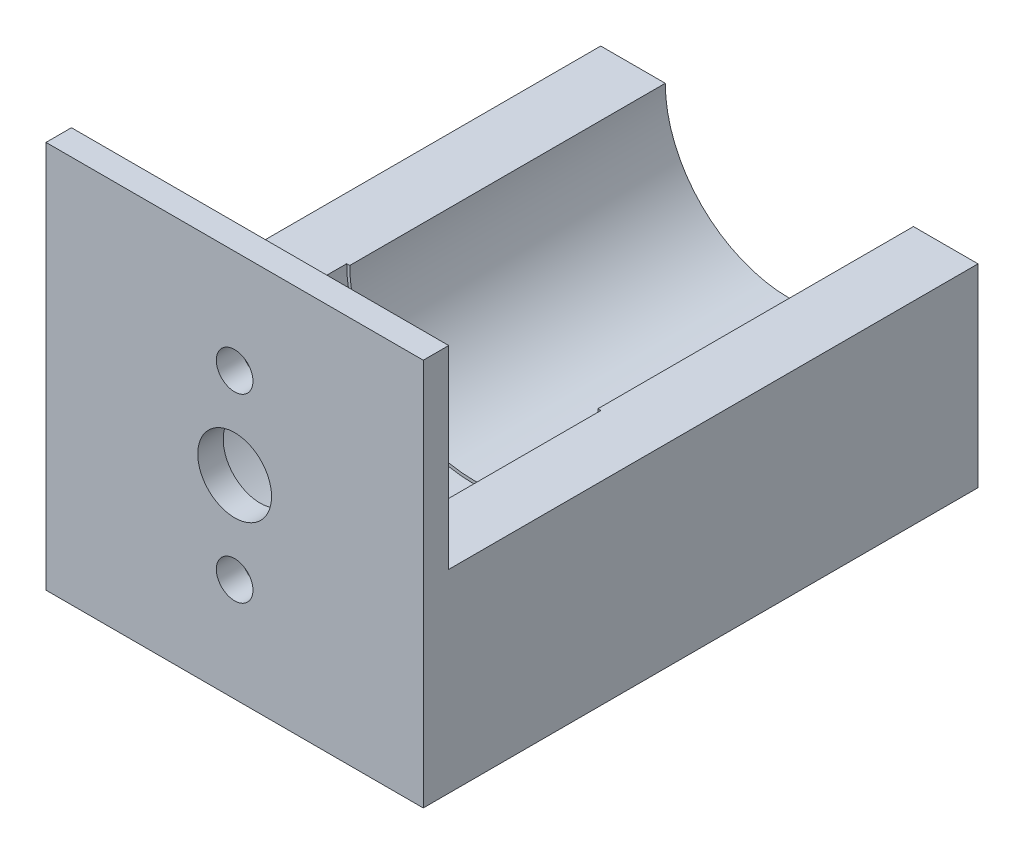
SolidWorks part; units mm, degrees
ref_plane "Front Plane" through (0, 0, 0) normal (0, 0, 1) x (1, 0, 0)
ref_plane "Top Plane" through (0, 0, 0) normal (0, 1, 0) x (1, 0, 0)
ref_plane "Right Plane" through (0, 0, 0) normal (1, 0, 0) x (0, 0, -1)
sketch "Sketch1" plane through (0, 0, 0) normal (0, 0, 1) x (1, 0, 0)
  line L7 (23.7638, 19.05) -> (23.7638, 0)
  line L10 (-13.3009, 19.05) -> (-13.3009, 0)
  line L12 (-13.3009, 19.05) -> (-6.9589, 19.05)
  line L13 (23.7638, 19.05) -> (17.4218, 19.05)
  line L14 (-13.3009, 0) -> (23.7638, 0)
  arc A1 (17.4218, 19.05) -> (-6.9589, 19.05) centre (5.2314, 19.05) cw
  dimension "D2" = 6.342
  dimension "D1" = 19.05
  dimension "D3" = 6.342
  dimension "D5" = 37.0648
extrude "Boss-Extrude1" add sketch "Sketch1" along normal blind 31
sketch "Sketch3" plane through (0, 0, 31) normal (0, 0, 1) x (1, 0, 0)
  line L1 (-13.3009, 19.05) -> (-13.3009, 0)
  line L3 (-13.3009, 0) -> (23.7638, 0)
  line L14 (-13.3009, 19.05) -> (-7.2589, 19.05)
  line L15 (-6.9589, 19.05) -> (-13.3009, 19.05) construction
  line L16 (17.7218, 19.05) -> (23.7638, 19.05)
  line L17 (23.7638, 19.05) -> (23.7638, 0)
  arc A0 (17.7218, 19.05) -> (-7.2589, 19.05) centre (5.2314, 19.05) cw
  dimension "D1" = 6.042
  dimension "D2" = 19.05
  dimension "D4" = 37.0648
extrude "Boss-Extrude2" add sketch "Sketch3" along normal blind 21
sketch "Sketch4" plane through (0, 0, 52) normal (0, 0, 1) x (1, 0, 0)
  line L1 (-13.3009, 0) -> (23.7638, 0)
  line L2 (-13.3009, 0) -> (-13.3009, 38.1)
  line L3 (-13.3009, 38.1) -> (23.7638, 38.1)
  line L4 (23.7638, 0) -> (23.7638, 38.1)
  circle A0 centre (5.2314, 19.05) radius 3.625
  circle A1 centre (5.2314, 10.16) radius 1.8
  circle A2 centre (5.2314, 27.94) radius 1.8
  dimension "D4" = 18.5324
  dimension "D5" = 7.25
  dimension "D6" = 3.6
  dimension "D7" = 3.6
  dimension "D10" = 8.89
  dimension "D11" = 8.89
  dimension "D1" = 37.0648
  dimension "D2" = 38.1
  dimension "D3" = 19.05
  dimension "D8" = 0
  dimension "D9" = 0
extrude "Boss-Extrude3" add sketch "Sketch4" along normal blind 2.5
sketch "Sketch5" plane through (0, 0, 0) normal (0, -1, 0) x (1, 0, 0)
  line L0 (-13.3009, 54.5) -> (-13.3009, 0) construction
  line L1 (-13.3009, 54.5) -> (23.7638, 54.5) construction
  line L2 (23.7638, 54.5) -> (23.7638, 0) construction
  line L3 (-13.3009, 0) -> (23.7638, 0) construction
  circle A0 centre (-6.9509, 48.15) radius 2
  circle A1 centre (17.4138, 48.15) radius 2
  circle A2 centre (-6.9509, 6.35) radius 2
  circle A3 centre (17.4138, 6.35) radius 2
  dimension "D1" = 4
  dimension "D2" = 4
  dimension "D3" = 4
  dimension "D4" = 4
  dimension "D6" = 6.35
  dimension "D7" = 6.35
  dimension "D8" = 6.35
  dimension "D9" = 6.35
  dimension "D10" = 6.35
  dimension "D11" = 6.35
  dimension "D12" = 6.35
  dimension "D5" = 6.35
extrude "Cut-Extrude1" cut sketch "Sketch5" against normal blind 7
